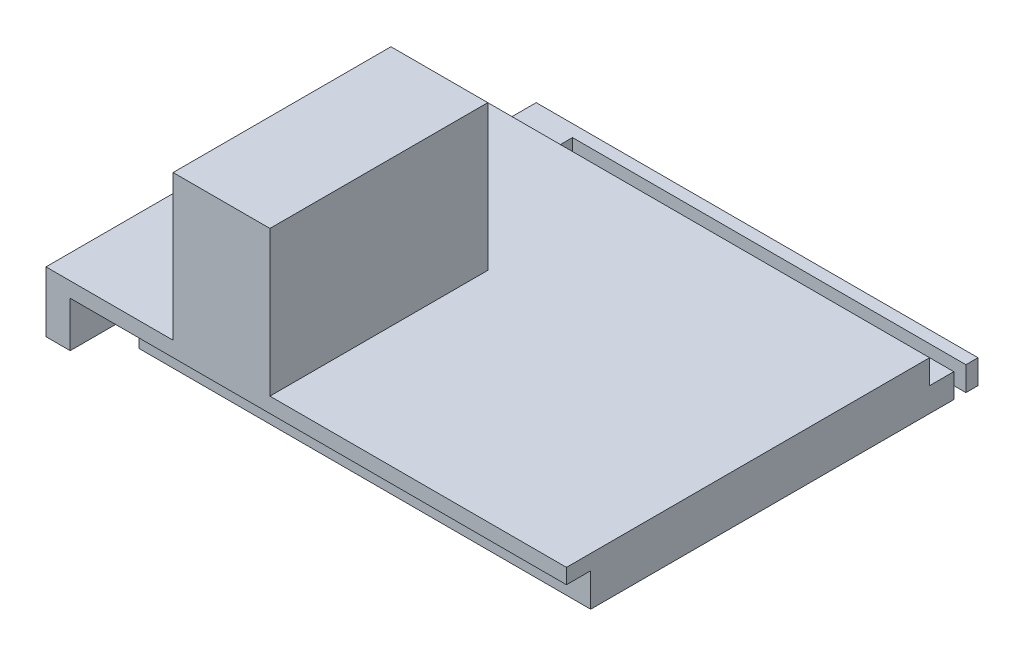
SolidWorks part; units mm, degrees
ref_plane "前视基准面" through (0, 0, 0) normal (0, 0, 1) x (1, 0, 0)
ref_plane "上视基准面" through (0, 0, 0) normal (0, 1, 0) x (1, 0, 0)
ref_plane "右视基准面" through (0, 0, 0) normal (1, 0, 0) x (0, 0, -1)
other "Configuration Table"
sketch "草图1" plane through (0, 0, 0) normal (0, 1, 0) x (1, 0, 0)
  line L0 (-26.5, 16) -> (-27.3, 16)
  line L1 (26.5, 16) -> (-26.5, 16)
  line L2 (26.5, 16) -> (26.5, -16)
  line L3 (26.5, -16) -> (-26.5, -16)
  line L4 (-26.5, 16) -> (-26.5, -16)
  line L5 (26.5, 16) -> (-26.5, -16) construction
  line L6 (26.5, -16) -> (-26.5, 16) construction
  line L7 (-27.3, 16) -> (-27.3, -16)
  line L8 (-27.3, -16) -> (-26.5, -16)
  line L9 (26.5, 16) -> (27.3, 16)
  line L10 (27.3, 16) -> (27.3, -16)
  line L11 (27.3, -16) -> (26.5, -16)
  line L12 (0, 0) -> (0, -17.2207) construction
  point P0 (0, 0)
  dimension "D1" = 53
  dimension "D2" = 32
  dimension "D3" = 0.8
  dimension "D4" = 0.8
extrude "凸台-拉伸1" add sketch "草图1" along normal blind 2 contours L1 L4 L3 L2 region at (0, 0, 0)
extrude "凸台-拉伸3" add sketch "草图1<5>" along normal blind 0.8 contours L7 L8 L4 L0 region at (-26.9, 0, 0)
sketch "草图1<5>" plane through (0, 0, 0) normal (0, 1, 0) x (1, 0, 0) same geometry as "草图1"
extrude "凸台-拉伸4" add sketch "草图1<6>" along normal blind 0.8 contours L11 L10 L9 L2 region at (26.9, 0, 0)
sketch "草图1<6>" plane through (0, 0, 0) normal (0, 1, 0) x (1, 0, 0) same geometry as "草图1"
sketch "草图3" plane through (0, 0, 0) normal (0, 1, 0) x (1, 0, 0)
  line L0 (-27.3, -16) -> (-27.3, -17)
  line L1 (-27.3, -17) -> (27.3, -17)
  line L2 (27.3, -17) -> (27.3, -16)
  line L3 (27.3, -16) -> (-27.3, -16)
  dimension "D1" = 1
extrude "凸台-拉伸5" add sketch "草图3" along normal blind 0.8
sketch "草图4" plane through (0, 0, 0) normal (0, 1, 0) x (1, 0, 0)
  line L0 (-22.5, -14) -> (22.5, -14)
  line L1 (22.5, -14) -> (22.5, -15)
  line L2 (22.5, -15) -> (-22.5, -15)
  line L3 (-22.5, -15) -> (-22.5, -14)
  line L4 (-26.5, 16) -> (-26.5, -16) construction
  line L5 (26.5, 16) -> (26.5, -16) construction
  line L6 (26.5, -16) -> (-26.5, -16) construction
  point P4 (-22.5, -14.5)
  dimension "D1" = 4
  dimension "D2" = 4
  dimension "D3" = 1
  dimension "D4" = 1
extrude "切除-拉伸1" cut sketch "草图4" along normal through all
extrude "凸台-拉伸6" add sketch "草图4<2>" along normal blind 2
sketch "草图4<2>" plane through (0, 0, 0) normal (0, 1, 0) x (1, 0, 0) same geometry as "草图4"
sketch "草图5" plane through (0, 0, 0) normal (0, 1, 0) x (1, 0, 0)
  line L0 (-22.5, 16) -> (-22.5, 15)
  line L1 (26.5, 16) -> (-26.5, 16) construction
  line L2 (-22.5, 15) -> (22.5, 15)
  line L3 (22.5, 15) -> (22.5, 16)
  line L4 (22.5, 16) -> (-22.5, 16)
  line L5 (-26.5, 16) -> (-26.5, -16) construction
  line L6 (26.5, 16) -> (26.5, -16) construction
  line L7 (-22.5, 15) -> (-22.5, 14)
  line L8 (-22.5, 14) -> (22.5, 14)
  line L9 (22.5, 14) -> (22.5, 15)
  dimension "D1" = 4
  dimension "D2" = 4
  dimension "D3" = 1
  dimension "D4" = 1
extrude "切除-拉伸2" cut sketch "草图5" along normal blind 2 contours L8 L9 L2 L7 region at (0, 0, -14.5)
sketch "草图6" plane through (0, 0, 0) normal (0, 1, 0) x (1, 0, 0)
  line L0 (-26.5, -16) -> (-27.3, -16)
  line L1 (-27.3, 16) -> (-27.3, -17) construction
  line L2 (-27.3, -16) -> (-27.3, -17)
  line L3 (-27.3, -17) -> (-26.5, -17)
  line L4 (-27.3, -17) -> (27.3, -17) construction
  line L5 (-26.5, -17) -> (-26.5, -16)
  line L6 (0, 0) -> (0, -50000) construction
  line L7 (27.3, -17) -> (26.5, -17)
  line L8 (26.5, -17) -> (26.5, -16)
  line L9 (26.5, -16) -> (27.3, -16)
  line L10 (27.3, -16) -> (27.3, -17)
extrude "切除-拉伸3" cut sketch "草图6" along normal blind 10
sketch "草图7" plane through (0, 0, 0) normal (0, 0, 1) x (1, 0, 0)
  line L0 (-24.5, 2) -> (-24.5, 4)
  line L1 (26.5, 2) -> (-26.5, 2) construction
  line L2 (-24.5, 4) -> (-33, 4)
  line L3 (-33, 4) -> (-33, -1)
  line L4 (-33, -1) -> (-31, -1)
  line L5 (-31, -1) -> (-31, 2)
  line L6 (-31, 2) -> (-24.5, 2)
  line L7 (-26.5, 2) -> (-26.5, 0.8) construction
  line L8 (0, 0) -> (0, -50000) construction
  line L9 (24.5, 2) -> (24.5, 4)
  line L10 (31, 2) -> (24.5, 2)
  line L11 (31, -1) -> (31, 2)
  line L12 (33, -1) -> (31, -1)
  line L13 (33, 4) -> (33, -1)
  line L14 (24.5, 4) -> (33, 4)
  dimension "D1" = 2
  dimension "D2" = 2
  dimension "D3" = 3
  dimension "D4" = 2
  dimension "D5" = 4.5
extrude "凸台-拉伸7" add sketch "草图7" along normal blind 18 and the other way blind 12
sketch "草图8" plane through (0, 0, 0) normal (0, 0, 1) x (1, 0, 0)
  line L0 (-24.5, 4) -> (-24.5, 2)
  line L1 (-24.5, 2) -> (24.5, 2)
  line L2 (24.5, 2) -> (24.5, 4)
  line L3 (24.5, 4) -> (-24.5, 4)
extrude "凸台-拉伸8" add sketch "草图8" along normal blind 18 and the other way blind 12
ref_plane "基准面1" through (10, 0, 0) normal (1, 0, 0) x (0, 0, -1)
sketch "草图9" plane through (10, 0, 0) normal (1, 0, 0) x (0, 0, -1)
  line L1 (-27.5739, 13.7253) -> (20.5975, 13.7253)
  line L2 (-27.5739, 13.7253) -> (-27.5739, -11.4884)
  line L3 (-27.5739, -11.4884) -> (20.5975, -11.4884)
  line L4 (20.5975, 13.7253) -> (20.5975, -11.4884)
sketch "草图12" plane through (0, 0, 0) normal (1, 0, 0) x (0, 0, -1)
  line L0 (-18, 2.7551) -> (-16, 2.7551)
  line L1 (-18, -1) -> (-18, 4) construction
  line L2 (-16, 2.7551) -> (-16, 2)
  line L3 (-16, 2) -> (-18, 2)
  line L4 (-18, 2) -> (-18, 2.7551)
  dimension "D1" = 2
extrude "切除-拉伸4" cut sketch "草图12" against normal up to surface and the other way up to surface up to face at (-31, 0.5, 3) other way up to face at (31, 0.5, 3)
extrude "切除-拉伸5" cut sketch "草图9" along normal up to next
sketch "草图13" plane through (10, 0, 0) normal (1, 0, 0) x (0, 0, -1)
  line L0 (-16, 0.8) -> (-16, 0)
  line L1 (14, 0) -> (-17, 0) construction
  line L2 (-16, 0) -> (-17, 0)
  line L3 (-17, 0) -> (-17, 0.8)
  line L4 (-17, 0.8) -> (-16, 0.8)
extrude "切除-拉伸6" cut sketch "草图13" against normal up to next
sketch "草图14" plane through (0, 0, 0) normal (0, 0, 1) x (1, 0, 0)
  line L0 (-26.5, 2) -> (-26.5, 16)
  line L1 (-26.5, 16) -> (-14.5, 16)
  line L2 (-14.5, 16) -> (-14.5, 4)
  line L3 (10, 4) -> (-33, 4) construction
  line L4 (-14.5, 4) -> (-22.5, 4)
  line L5 (-22.5, 4) -> (-22.5, 16)
  dimension "D1" = 4
  dimension "D2" = 8
  dimension "D3" = 12
extrude "凸台-拉伸9" add sketch "草图14" along normal through all contours L5 L4 L2 L1 region at (-18.5, 10, 0)
